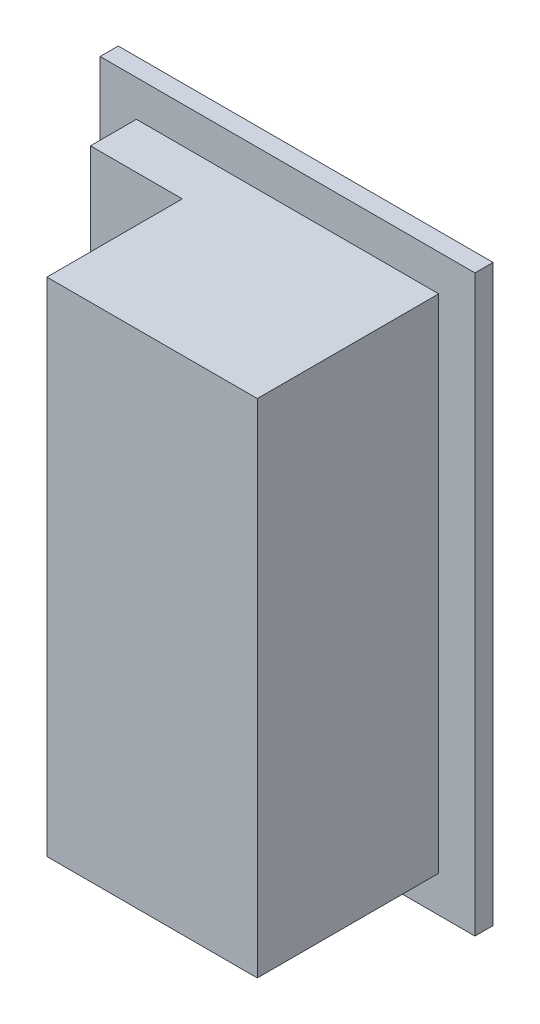
SolidWorks part; units mm, degrees
ref_plane "Plano frontal" through (0, 0, 0) normal (0, 0, 1) x (1, 0, 0)
ref_plane "Plano superior" through (0, 0, 0) normal (0, 1, 0) x (1, 0, 0)
ref_plane "Plano direito" through (0, 0, 0) normal (1, 0, 0) x (0, 0, -1)
sketch "Esboço1" plane through (0, 0, 0) normal (0, 0, 1) x (1, 0, 0)
  line L0 (0, 40.5) -> (23, 40.5)
  line L1 (0, 0) -> (24, 0)
  line L2 (0, 0) -> (0, 41.5)
  line L3 (0, 41.5) -> (24, 41.5)
  line L4 (24, 0) -> (24, 41.5)
  line L5 (-4, -3) -> (27, -3)
  line L6 (-4, -3) -> (-4, 44.5)
  line L7 (-4, 44.5) -> (27, 44.5)
  line L8 (27, -3) -> (27, 44.5)
  line L9 (23, 40.5) -> (23, 1)
  line L10 (23, 1) -> (0, 1)
  dimension "D1" = 24
  dimension "D2" = 41.5
  dimension "D3" = 3
  dimension "D4" = 4
  dimension "D5" = 3
  dimension "D6" = 3
  dimension "D7" = 1
  dimension "D8" = 1
  dimension "D9" = 1
extrude "Ressalto-extrusão1" add sketch "Esboço1" along normal blind 1.5 contours L5 L8 L7 L6 L4 L1 L2 L3 region at (-3.4328, 20.75, 0)
extrude "Ressalto-extrusão2" add sketch "Esboço1<4>" along normal blind 16.5 contours L9 L10 L2 L1 L4 L3 L0 region at (0.4794, 41, 0)
sketch "Esboço1<4>" plane through (0, 0, 0) normal (0, 0, 1) x (1, 0, 0) same geometry as "Esboço1"
extrude "Ressalto-extrusão3" add sketch "Esboço1<5>" against normal blind 1 from surface contours L10 L9 L0 L2 region at (11.5, 20.75, 0) starting at face at (11.75, 20.75, 16.5)
sketch "Esboço1<5>" plane through (0, 0, 0) normal (0, 0, 1) x (1, 0, 0) same geometry as "Esboço1"
sketch "Esboço2" plane through (0, 0, 16.5) normal (0, 0, 1) x (1, 0, 0)
  line L0 (0, 41.5) -> (24, 41.5) construction
  line L1 (0, 0) -> (6.6, 0)
  line L2 (0, 0) -> (0, 41.5)
  line L3 (0, 41.5) -> (6.6, 41.5)
  line L4 (6.6, 0) -> (6.6, 41.5)
  dimension "D1" = 6.6
extrude "Corte-extrusão1" cut sketch "Esboço2" against normal up to surface (15 mm away) up to face at (8, 20.75, 1.5)
sketch "Esboço3" plane through (0, 41.5, 0) normal (0, 1, 0) x (1, 0, 0)
  line L0 (-1, -1.5) -> (-1, -5.3)
  line L1 (-1, -5.3) -> (6.6, -5.3)
  line L2 (6.6, -1.5) -> (6.6, -16.5) construction
  line L3 (6.6, -4.3) -> (0, -4.3)
  line L4 (0, -4.3) -> (0, -1.5)
  line L5 (0, -1.5) -> (-1, -1.5)
  line L6 (6.6, -4.3) -> (6.6, -5.3)
  point P2 (0, 0)
  point P10 (0, 0)
  dimension "D1" = 1
  dimension "D2" = 1
  dimension "D3" = 3.8
extrude "Ressalto-extrusão6" add sketch "Esboço3" against normal up to surface (40.5 mm away) from surface separate body up to face at (9.8667, 1, 5.6667) starting at face at (9.8667, 40.5, 5.6667)
sketch "Esboço4" plane through (6.6, 0, 0) normal (-1, 0, 0) x (0, 0, 1)
  line L1 (1.5, 41.5) -> (5.3, 41.5)
  line L2 (1.5, 41.5) -> (1.5, 40.5)
  line L3 (1.5, 40.5) -> (5.3, 40.5)
  line L4 (5.3, 41.5) -> (5.3, 40.5)
  line L5 (1.5, 0) -> (5.3, 0)
  line L6 (1.5, 0) -> (1.5, 1)
  line L7 (1.5, 1) -> (5.3, 1)
  line L8 (5.3, 0) -> (5.3, 1)
extrude "Ressalto-extrusão9" add sketch "Esboço4" along normal up to surface (7.6 mm away) up to face at (-1, 20.75, 3.4)
